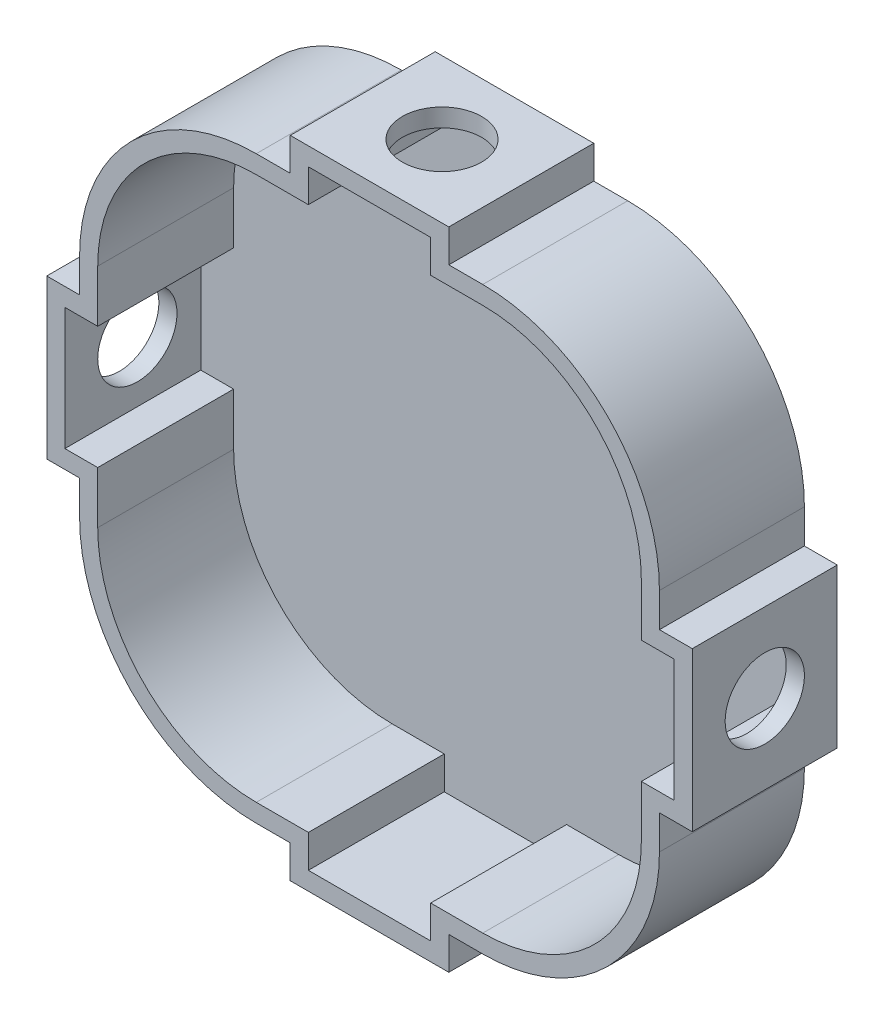
SolidWorks part; units mm, degrees
ref_plane "Спереди" through (0, 0, 0) normal (0, 0, 1) x (1, 0, 0)
ref_plane "Сверху" through (0, 0, 0) normal (0, 1, 0) x (1, 0, 0)
ref_plane "Справа" through (0, 0, 0) normal (1, 0, 0) x (0, 0, -1)
sketch "Эскиз-База" plane through (0, 0, 0) normal (0, 0, 1) x (1, 0, 0)
  line L0 (28.5, 0) -> (-28.5, 0) construction
  line L1 (-25.6, 25.6) -> (25.6, 25.6) construction
  line L2 (-25.6, 25.6) -> (-25.6, -25.6) construction
  line L3 (-25.6, -25.6) -> (25.6, -25.6) construction
  line L4 (25.6, 25.6) -> (25.6, -25.6) construction
  line L5 (-25.6, 25.6) -> (25.6, -25.6) construction
  line L6 (-25.6, -25.6) -> (25.6, 25.6) construction
  line L7 (0, -25.6) -> (0, 28.5) construction
  line L8 (-25.6, 7) -> (-28.5, 7)
  line L9 (-28.5, 7) -> (-28.5, -7)
  line L10 (-28.5, -7) -> (-25.6, -7)
  line L11 (25.6, 7) -> (28.5, 7)
  line L12 (28.5, 7) -> (28.5, -7)
  line L13 (28.5, -7) -> (25.6, -7)
  line L14 (-25.6, 10) -> (-25.6, 7)
  line L15 (-25.6, -10) -> (-25.6, -7)
  line L16 (-10, -25.6) -> (-7, -25.6)
  line L17 (25.6, -10) -> (25.6, -7)
  line L18 (25.6, 7) -> (25.6, 10)
  line L19 (-7, 25.6) -> (-7, 28.5)
  line L20 (-7, 28.5) -> (7, 28.5)
  line L21 (7, 28.5) -> (7, 25.6)
  line L22 (7, -28.5) -> (7, -25.6)
  line L23 (-7, -28.5) -> (7, -28.5)
  line L24 (-7, -25.6) -> (-7, -28.5)
  line L25 (-10, 25.6) -> (-7, 25.6)
  line L26 (7, 25.6) -> (10, 25.6)
  line L27 (7, -25.6) -> (10, -25.6)
  arc A0 (-25.6, 10) -> (-10, 25.6) centre (-10, 10) cw
  arc A1 (25.6, 10) -> (10, 25.6) centre (10, 10) ccw
  arc A2 (25.6, -10) -> (10, -25.6) centre (10, -10) cw
  arc A3 (-25.6, -10) -> (-10, -25.6) centre (-10, -10) ccw
  point P0 (0, 0)
  point P17 (-28.5, 0)
  point P24 (28.5, 0)
  point P36 (0, 28.5)
  dimension "D2" = 15.6
  dimension "D3" = 15.6
  dimension "D5" = 57
  dimension "D6" = 14
  dimension "D1" = 51.2
  dimension "D4" = 14
  dimension "D7" = 57
extrude "Вытянуть-Стенки" add sketch "Эскиз-База" along normal blind 12 thin thin type one direction reverse wall 1.6
extrude "Бобышка-Дно" add sketch "Эскиз-База<8>" against normal blind 0.8
sketch "Эскиз-База<8>" plane through (0, 0, 0) normal (0, 0, 1) x (1, 0, 0) same geometry as "Эскиз-База"
sketch "Эскиз-Левое отверстие" plane through (-28.5, 0, 0) normal (-1, 0, 0) x (0, 0, 1)
  line L0 (-0.8, 7) -> (12, -7) construction
  line L1 (-0.8, -7) -> (12, 7) construction
  circle A0 centre (5.6, 0) radius 3.5
  dimension "D1" = 7
extrude "Вырез-Отверстия слева справа" cut sketch "Эскиз-Левое отверстие" against normal up to surface (57 mm away)
sketch "Эскиз-Отверстие сверху" plane through (0, 28.5, 0) normal (0, 1, 0) x (1, 0, 0)
  line L0 (-7, 0.8) -> (7, -12) construction
  line L1 (-7, -12) -> (7, 0.8) construction
  circle A0 centre (0, -5.6) radius 3.5
  dimension "D1" = 7
extrude "Вырез-Верхнее отверстие" cut sketch "Эскиз-Отверстие сверху" against normal up to next
